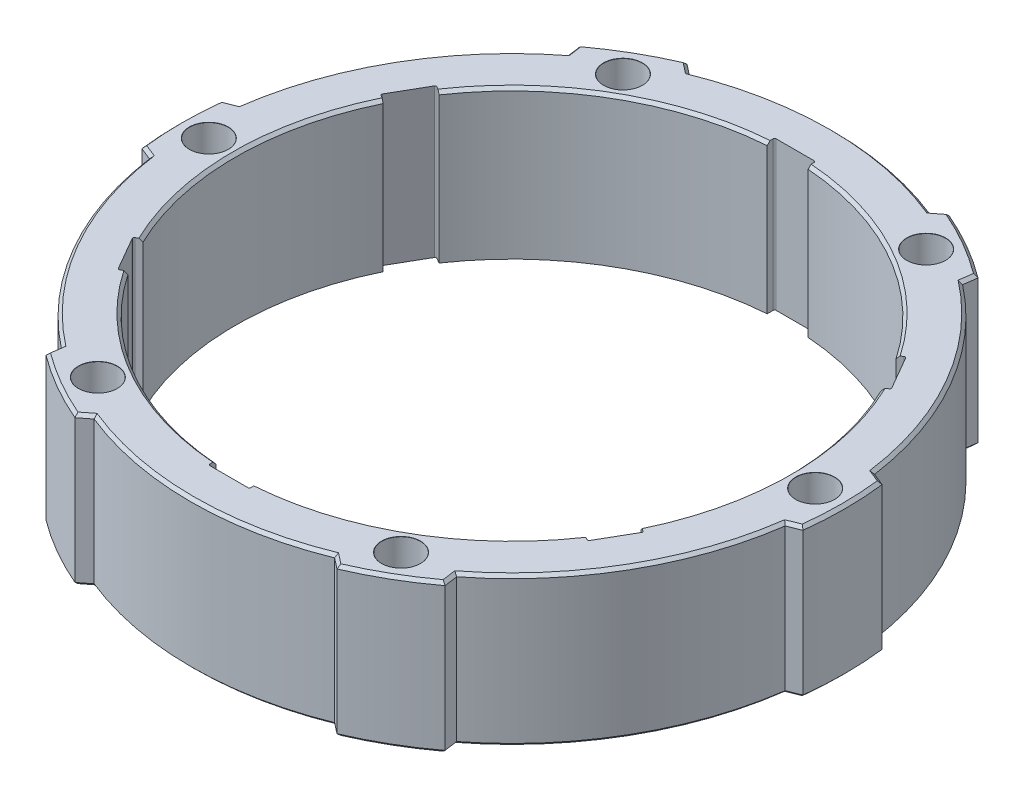
SolidWorks part; units mm, degrees
material "PET"
ref_plane "Front Plane" through (0, 0, 0) normal (0, 0, 1) x (1, 0, 0)
ref_plane "Top Plane" through (0, 0, 0) normal (0, 1, 0) x (1, 0, 0)
ref_plane "Right Plane" through (0, 0, 0) normal (1, 0, 0) x (0, 0, -1)
sketch "body_sketch" plane through (0, 0, 0) normal (0, 1, 0) x (1, 0, 0)
  circle A0 centre (0, 0) radius 56
  circle A1 centre (0, 0) radius 46.5
  dimension "D1" = 93
  dimension "D2" = 112
extrude "body" add sketch "body_sketch" along normal blind 25
sketch "hole_pos" plane through (0, 25, 0) normal (0, 1, 0) x (1, 0, 0)
  point P9 (51, 0)
  dimension "D1" = 51
hole_wizard "spring_screw_hole" positions "hole_pos" profile "Sketch4" counterbore size "M3" standard "DIN" end condition through all
sketch "Sketch4" plane through (51, 25, 0) normal (1, 0, 0) x (0, 0, 1)
  line L0 (0, 0) -> (0, 25)
  line L1 (0, 25) -> (1.7, 25)
  line L3 (1.7, 25) -> (1.7, 20)
  line L4 (3.25, 20) -> (1.7, 20)
  line L5 (3.25, 20) -> (3.25, 0.025)
  line L6 (3.25, 0.025) -> (3.275, 0)
  line L7 (3.275, 0) -> (0, 0)
  line L8 (-3.25, 0.025) -> (-3.275, 0) construction
  line L11 (0, -6.35) -> (0, 107.95) construction
  dimension "Thru Hole Dia." = 3.4
  dimension "Thru Hole Depth" = 25
  dimension "C'Bore Dia." = 6.5
  dimension "C'Bore Depth" = 20
  dimension "Near C'Sink Dia." = 6.55
  dimension "Near C'Sink Angle" = 90
sketch "Sketch5" plane through (0, 25, 0) normal (0, 1, 0) x (1, 0, 0)
  line L10 (53.4745, 7.5153) -> (55.6031, 6.6553)
  line L11 (33.2457, 42.5526) -> (33.5652, 44.8261)
  line L12 (0, 0) -> (51, 0) construction
  arc A0 (53.4745, 7.5153) -> (33.2457, 42.5526) centre (0, 0) ccw
  circle A1 centre (51, 0) radius 1.7 construction
  circle A3 centre (0, 0) radius 56 construction
  arc A4 (33.5652, 44.8261) -> (55.6031, 6.6553) centre (0, 0) cw
  dimension "D3" = 54
  dimension "D4" = 22
  dimension "D5" = 82
  dimension "D1" = 8
  dimension "D2" = 44
extrude "side_cutouts" cut sketch "Sketch5" against normal through all
sketch "Sketch6" plane through (0, 25, 0) normal (0, 1, 0) x (1, 0, 0)
  line L0 (0, 0) -> (51, 0) construction
  line L1 (41.8825, 20.2017) -> (38.4364, 26.1704)
  line L2 (38.4364, 26.1704) -> (39.519, 26.7954)
  line L3 (39.519, 26.7954) -> (42.965, 20.8267)
  line L4 (42.965, 20.8267) -> (41.8825, 20.2017)
  line L5 (0, 0) -> (38.4364, 26.1704) construction
  line L6 (0, 0) -> (41.8825, 20.2017) construction
  circle A0 centre (0, 0) radius 46.5 construction
  dimension "D1" = 25.75
  dimension "D2" = 8.5
  dimension "D3" = 1.25
extrude "driving_cutout" cut sketch "Sketch6" against normal through all
fillet "driving_cutout_fillet" radius 0.25 2 edges at (42.965, 12.5, -20.8267) (39.519, 12.5, -26.7954)
pattern_circular "main_pattern" count 6 over 360 about axis through (0, 25, 0) along (0, 1, 0) of "spring_screw_hole", "side_cutouts", "driving_cutout", "driving_cutout_fillet"
chamfer "overall_chamfer" distance 0.5 angle 45 54 edges at (46.7654, 0, -27) (54.5388, 0, -7.0853) (56, 0, 0) (54.5388, 0, 7.0853) (46.7654, 0, 27) (33.4055, 0, 43.6893) (28, 0, 48.4974) (21.1333, 0, 50.7747) (0, 0, 54) (-21.1333, 0, 50.7747) (-28, 0, 48.4974) (-33.4055, 0, 43.6893) (-46.7654, 0, 27) (-54.5388, 0, 7.0853) (-56, 0, 0) (-54.5388, 0, -7.0853) (-46.7654, 0, -27) (-33.4055, 0, -43.6893) (-28, 0, -48.4974) (-21.1333, 0, -50.7747) (0, 0, -54) (21.1333, 0, -50.7747) (33.4055, 0, -43.6893) (28, 0, -48.4974) (33.4055, 25, 43.6893) (28, 25, 48.4974) (21.1333, 25, 50.7747) (0, 25, 54) (-21.1333, 25, 50.7747) (-28, 25, 48.4974) (-33.4055, 25, 43.6893) (-46.7654, 25, 27) (-54.5388, 25, 7.0853) (-56, 25, 0) (-54.5388, 25, -7.0853) (-46.7654, 25, -27) (-33.4055, 25, -43.6893) (-28, 25, -48.4974) (-21.1333, 25, -50.7747) (0, 25, -54) (21.1333, 25, -50.7747) (28, 25, -48.4974) (33.4055, 25, -43.6893) (46.7654, 25, -27) (54.5388, 25, -7.0853) (56, 25, 0) (54.5388, 25, 7.0853) (46.7654, 25, 27) (-46.5, 25, 0) (-23.25, 25, 40.2702) (23.25, 25, 40.2702) (46.5, 25, 0) (23.25, 25, -40.2702) (-23.25, 25, -40.2702)
equation "\"paper_size\" = 600mm"
equation "\"cb_roll_d_outer\" = 86mm"
equation "\"cb_roll_d_inner\" = 76mm"
equation "\"helper_d\" = 92mm"
equation "\"outer_d\" = 112mm"
equation "\"spring_l_max\" = 25mm"
equation "\"spring_l_min\" = 10mm"
equation "\"D2@body_sketch\"=\"outer_d\""
equation "\"D1@body_sketch\"=\"helper_d\" + 1"
equation "\"C'Bore Depth@Sketch4\"=\"spring_l_max\" - \"spring_l_min\" + 5"
equation "\"D3@Sketch5\"=\"outer_d\" / 2 - 2"
equation "\"D1@hole_pos\"=(\"outer_d\" + \"helper_d\") / 4"
equation "\"D1@body\"=\"spring_l_max\" - \"spring_l_min\" + 10"
